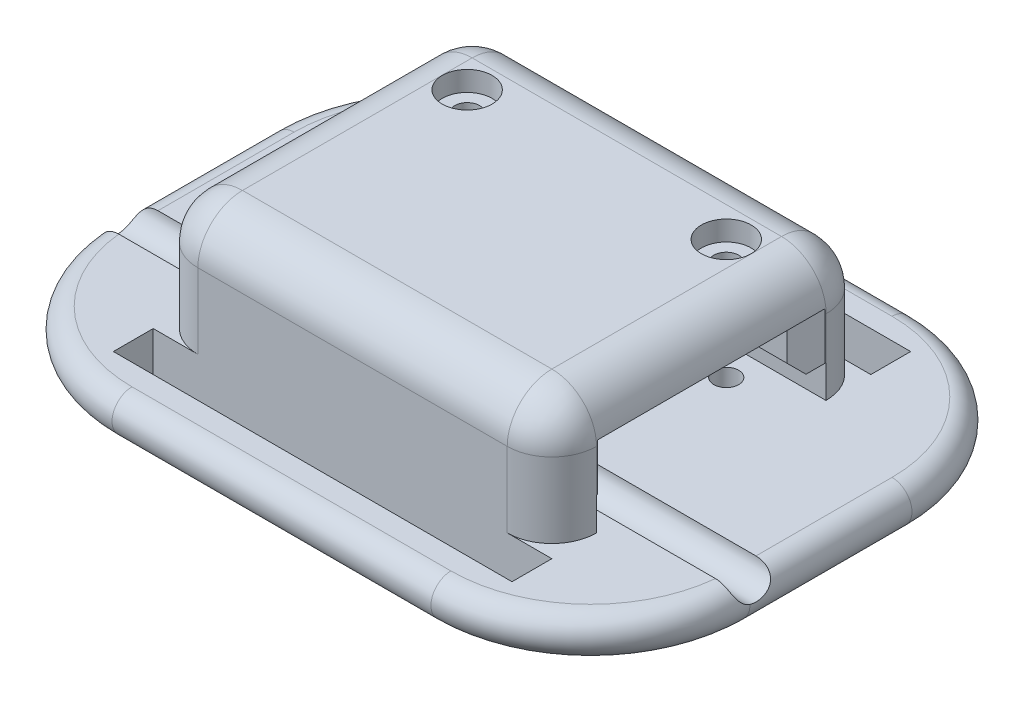
SolidWorks part; units mm, degrees
ref_plane "Front Plane" through (0, 0, 0) normal (0, 0, 1) x (1, 0, 0)
ref_plane "Top Plane" through (0, 0, 0) normal (0, 1, 0) x (1, 0, 0)
ref_plane "Right Plane" through (0, 0, 0) normal (1, 0, 0) x (0, 0, -1)
sketch "Sketch1" plane through (0, 0, 0) normal (0, 1, 0) x (1, 0, 0)
  line L1 (-7.9604, 16.7072) -> (23.7896, 16.7072)
  line L2 (-7.9604, 16.7072) -> (-7.9604, -8.6928)
  line L3 (-7.9604, -8.6928) -> (23.7896, -8.6928)
  line L4 (23.7896, 16.7072) -> (23.7896, -8.6928)
  dimension "D1" = 31.75
  dimension "D2" = 25.4
extrude "Boss-Extrude1" add sketch "Sketch1" along normal blind 12.7
sketch "Sketch2" plane through (23.7896, 0, 0) normal (1, 0, 0) x (0, 0, -1)
  line L0 (-8.6928, 12.7) -> (16.7072, 0) construction
  line L1 (16.7072, 12.7) -> (-8.6928, 0) construction
  line L3 (-5.1209, 3.175) -> (13.1353, 3.175)
  line L4 (-5.1209, 3.175) -> (-5.1209, 9.525)
  line L5 (-5.1209, 9.525) -> (13.1353, 9.525)
  line L6 (13.1353, 3.175) -> (13.1353, 9.525)
  line L7 (-5.1209, 3.175) -> (13.1353, 9.525) construction
  line L8 (-5.1209, 9.525) -> (13.1353, 3.175) construction
  point P4 (4.0072, 6.35)
  point P10 (4.0072, 6.35)
  dimension "D1" = 18.2562
  dimension "D2" = 6.35
extrude "Cut-Extrude3" cut sketch "Sketch2" against normal through all
sketch "Sketch4" plane through (23.7896, 0, 0) normal (1, 0, 0) x (0, 0, -1)
  line L0 (-5.1209, 3.175) -> (13.1353, 3.175) construction
  line L1 (-5.1209, 9.525) -> (-3.5334, 9.525)
  line L2 (-5.1209, 9.525) -> (-5.1209, 4.7625)
  line L3 (-5.1209, 4.7625) -> (-3.5334, 4.7625)
  line L4 (-3.5334, 9.525) -> (-3.5334, 4.7625)
  line L5 (4.0072, 9.525) -> (4.0072, 3.175) construction
  line L6 (13.1353, 4.7625) -> (11.5478, 4.7625)
  line L7 (11.5478, 9.525) -> (11.5478, 4.7625)
  line L8 (13.1353, 9.525) -> (11.5478, 9.525)
  line L9 (13.1353, 9.525) -> (13.1353, 4.7625)
  dimension "D1" = 1.5875
  dimension "D2" = 1.5875
extrude "Boss-Extrude2" add sketch "Sketch4" against normal through all
sketch "Sketch5" plane through (0, 3.175, 0) normal (0, 1, 0) x (1, 0, 0)
  line L0 (-4.7854, 13.1353) -> (-2.4042, 13.1353) construction
  line L1 (-4.7854, -5.1209) -> (20.6146, -5.1209) construction
  line L2 (-4.7854, -5.1209) -> (-4.7854, 13.1353) construction
  line L8 (-4.7854, 13.1353) -> (20.6146, 13.1353) construction
  line L9 (20.6146, -5.1209) -> (20.6146, 13.1353) construction
  line L10 (-4.7854, -5.1209) -> (20.6146, 13.1353) construction
  line L11 (-4.7854, 13.1353) -> (20.6146, -5.1209) construction
  line L12 (-2.4042, 13.1353) -> (-2.4042, 10.7541) construction
  line L13 (7.9146, 4.0072) -> (7.9146, 5.4175) construction
  circle A0 centre (-2.4042, 10.7541) radius 0.9922
  circle A1 centre (18.2333, 10.7541) radius 0.9922
  point P0 (7.9146, 4.0072)
  point P1 (7.9146, 4.0072)
  point P6 (7.9146, 4.0072)
  dimension "D1" = 25.4
  dimension "D2" = 18.2562
extrude "Cut-Extrude5" cut sketch "Sketch5" against normal through all and the other way through all
sketch "Sketch6" plane through (0, 0, 0) normal (0, -1, 0) x (1, 0, 0)
  line L1 (-0.0229, -10.7541) -> (-1.2136, -8.6919)
  line L2 (-1.2136, -8.6919) -> (-3.5948, -8.6919)
  line L3 (-3.5948, -8.6919) -> (-4.7854, -10.7541)
  line L4 (-4.7854, -10.7541) -> (-3.5948, -12.8163)
  line L5 (-3.5948, -12.8163) -> (-1.2136, -12.8163)
  line L6 (-1.2136, -12.8163) -> (-0.0229, -10.7541)
  line L7 (20.6146, -10.7541) -> (19.4239, -8.6919)
  line L8 (19.4239, -8.6919) -> (17.0427, -8.6919)
  line L9 (17.0427, -8.6919) -> (15.8521, -10.7541)
  line L10 (15.8521, -10.7541) -> (17.0427, -12.8163)
  line L11 (17.0427, -12.8163) -> (19.4239, -12.8163)
  line L12 (19.4239, -12.8163) -> (20.6146, -10.7541)
  circle A0 centre (-2.4042, -10.7541) radius 2.3813 construction
  circle A1 centre (18.2333, -10.7541) radius 2.3813 construction
extrude "Cut-Extrude6" cut sketch "Sketch6" against normal blind 1.5875
sketch "Sketch7" plane through (0, 12.7, 0) normal (0, 1, 0) x (1, 0, 0)
  circle A0 centre (-2.4042, 10.7541) radius 1.9844
  circle A1 centre (18.2333, 10.7541) radius 1.9844
extrude "Cut-Extrude7" cut sketch "Sketch7" against normal blind 1.5875
sketch "Sketch8" plane through (0, 0, 0) normal (0, -1, 0) x (1, 0, 0)
  line L1 (-17.4854, -23.1602) -> (33.3146, -23.1602)
  line L2 (-17.4854, -23.1602) -> (-17.4854, 15.1457)
  line L3 (-17.4854, 15.1457) -> (33.3146, 15.1457)
  line L4 (33.3146, -23.1602) -> (33.3146, 15.1457)
  line L5 (-17.4854, -23.1602) -> (33.3146, 15.1457) construction
  line L6 (-17.4854, 15.1457) -> (33.3146, -23.1602) construction
  line L7 (-7.9604, 8.6928) -> (23.7896, 8.6928)
  line L8 (-7.9604, 8.6928) -> (-7.9604, -16.7072)
  line L9 (-7.9604, -16.7072) -> (23.7896, -16.7072)
  line L10 (23.7896, 8.6928) -> (23.7896, -16.7072)
  point P0 (7.9146, -4.0072)
  point P9 (0, 0)
  point P10 (7.9146, -4.0072)
extrude "Boss-Extrude3" add sketch "Sketch8" against normal up to surface (3.175 mm away) contours L8 L7 L10 L9 | L2 L1 L4 L3 up to face at (-2.4042, 3.175, -11.7463)
sketch "Sketch10" plane through (0, 3.175, 0) normal (0, 1, 0) x (1, 0, 0)
  line L0 (-7.9604, 4.0072) -> (23.7896, 4.0072) construction
  line L1 (-7.9604, 16.7072) -> (23.7896, 16.7072)
  line L2 (-7.9604, 16.7072) -> (-7.9604, 19.8822)
  line L3 (-7.9604, 19.8822) -> (23.7896, 19.8822)
  line L4 (23.7896, 16.7072) -> (23.7896, 19.8822)
  line L5 (-7.9604, -11.8678) -> (23.7896, -11.8678)
  line L6 (23.7896, -8.6928) -> (23.7896, -11.8678)
  line L7 (-7.9604, -8.6928) -> (23.7896, -8.6928)
  line L8 (-7.9604, -8.6928) -> (-7.9604, -11.8678)
  dimension "D1" = 3.175
extrude "Cut-Extrude8" cut sketch "Sketch10" against normal through all
fillet "Fillet6" radius 12.7 4 edges at (-17.4854, 1.5875, 15.1457) (-17.4854, 1.5875, -23.1602) (33.3146, 1.5875, -23.1602) (33.3146, 1.5875, 15.1457)
chamfer "Chamfer1" distance 1.016 angle 45 6 edges at (-5.48, 4.7625, -11.5478) (-7.9604, 4.7625, -12.3416) (-7.9604, 4.7625, 4.3272) (7.9146, 4.7625, 3.5334) (23.7896, 4.7625, 4.3272) (23.7896, 4.7625, -12.3416)
chamfer "Chamfer2" distance 1.524 angle 45 4 edges at (-7.9604, 7.6518, -11.5478) (-7.9604, 7.6517, 3.5334) (23.7896, 7.6517, 3.5334) (23.7896, 7.6518, -11.5478)
fillet "Fillet7" radius 3.556 8 edges at (7.9146, 12.7, 8.6928) (23.7896, 7.9375, 8.6928) (23.7896, 12.7, -4.0072) (23.7896, 7.9375, -16.7072) (-7.9604, 12.7, -4.0072) (7.9146, 12.7, -16.7072) (-7.9604, 7.9375, 8.6928) (-7.9604, 7.9375, -16.7072)
fillet "Fillet10" 2 edges at (-13.7657, 0, 11.426) (-13.7657, 3.175, 11.426) type full round first side face at (7.9146, 0, -18.2947) second side face at (7.9146, 3.175, -16.0639) middle face at (-12.4506, 1.5875, 10.1109)
sketch "Sketch11" plane through (0, 0, 0) normal (1, 0, 0) x (0, 0, -1)
  line L0 (13.1512, 3.175) -> (9.9762, 3.175)
  line L1 (4.0072, 9.525) -> (4.0072, 3.175) construction
  circle A0 centre (9.9762, 3.175) radius 1.5875
  circle A1 centre (-1.9618, 3.175) radius 1.5875
extrude "Cut-Extrude10" cut sketch "Sketch11" against normal through all and the other way through all contours A1
